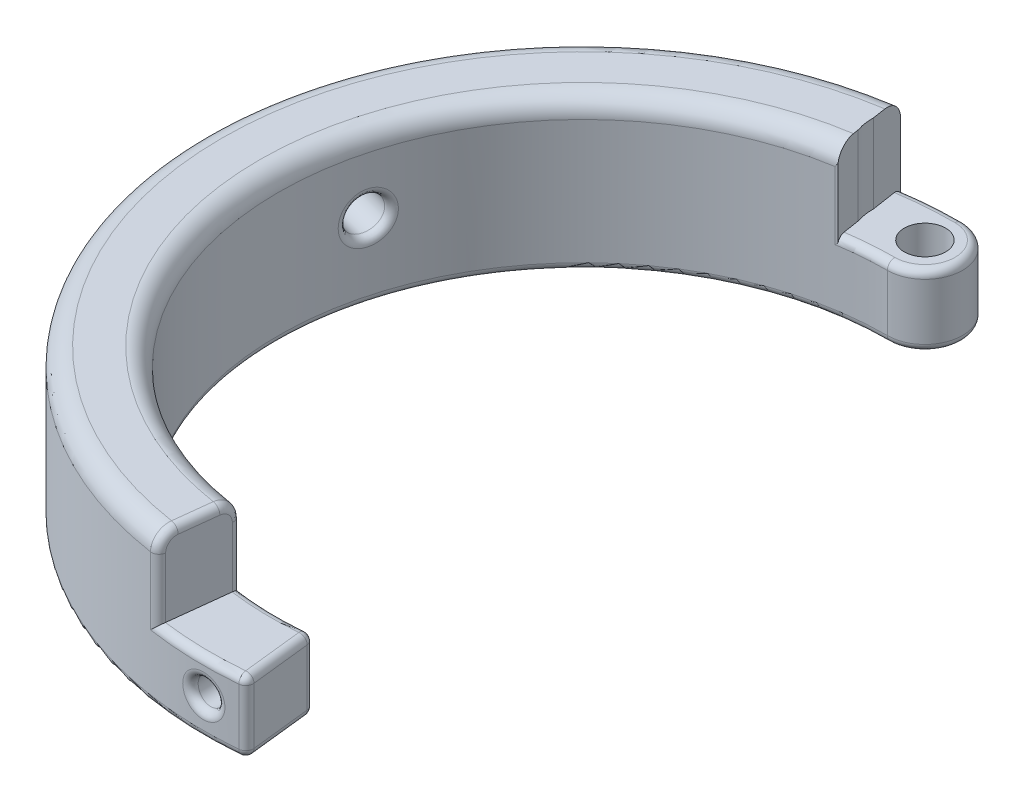
SolidWorks part; units mm, degrees
ref_plane "Front Plane" through (0, 0, 0) normal (0, 0, 1) x (1, 0, 0)
ref_plane "Top Plane" through (0, 0, 0) normal (0, 1, 0) x (1, 0, 0)
ref_plane "Right Plane" through (0, 0, 0) normal (1, 0, 0) x (0, 0, -1)
sketch "Sketch1" plane through (0, 0, 0) normal (0, 1, 0) x (1, 0, 0)
  line L0 (0, 50.5) -> (29.9823, 50.5) construction
  line L1 (0, 0) -> (0, 45.5) construction
  line L2 (0, 0) -> (-39.4042, -22.75) construction
  line L3 (4.5591, -41.2367) -> (5.4385, -49.1902)
  line L4 (0, 0) -> (4.4505, -40.2547) construction
  circle A0 centre (0, 45.5) radius 2.75
  arc A1 (0, 50.5) -> (0, 40.5) centre (0, 45.5) cw
  arc A2 (0, 50.5) -> (0, -50.5) centre (0, 0) ccw
  arc A3 (0, 40.5) -> (0, -40.5) centre (0, 0) ccw
  arc A4 (0, -40.5) -> (0, -50.5) centre (0, -45.5) cw construction
  circle A5 centre (-39.4042, -22.75) radius 2.75
  arc A6 (0, -40.5) -> (3.4793, -40.3503) centre (0, 0) ccw
  arc A7 (0, -50.5) -> (4.5343, -50.296) centre (0, 0) ccw
  arc A8 (4.5343, -50.296) -> (5.4385, -49.1902) centre (4.4445, -49.3001) ccw
  arc A9 (3.4793, -40.3503) -> (4.5591, -41.2367) centre (3.5652, -41.3466) cw
  dimension "D1" = 5.5
  dimension "D7" = 1
  dimension "D2" = 10
  dimension "D3" = 40.5
  dimension "D5" = 120
  dimension "D6" = 45.5
  dimension "D4" = 2
extrude "Boss-Extrude1" add sketch "Sketch1" along normal blind 20
sketch "Sketch3" plane through (0, 0, 0) normal (0, 0, 1) x (1, 0, 0)
  line L0 (4.5343, 20) -> (-50.5, 20) construction
  circle A0 centre (0, 15) radius 1.75
  circle A1 centre (0, 5) radius 1.75
  dimension "D1" = 3.5
  dimension "D4" = 3.5
  dimension "D2" = 5
  dimension "D3" = 5
extrude "Cut-Extrude2" cut sketch "Sketch3" along normal blind 71
sketch "Sketch2" plane through (0, 20, 0) normal (0, 1, 0) x (1, 0, 0)
  line L0 (0, -1000) -> (0, 49000) construction
  line L1 (5.4385, -49.1902) -> (4.5591, -41.2367)
  line L2 (5.4385, -49.1902) -> (4.5591, -41.2367) construction
  line L3 (-5.4385, -49.1902) -> (-4.5591, -41.2367) construction
  line L4 (-4.4505, -40.2547) -> (0, 0) construction
  line L5 (0, 0) -> (-5.5107, 35.9551) construction
  line L6 (0, 45.5) -> (-4.3301, 48) construction
  line L7 (0, 45.5) -> (-39.4042, -22.75) construction
  line L11 (-6.1357, 40.0325) -> (-6.1431, 40.0808) construction
  line L12 (-6.1431, 40.0808) -> (-6.629, 43.2514)
  line L13 (-5.5107, 35.9551) -> (-6.1357, 40.0325) construction
  line L16 (-6.629, 43.2514) -> (-6.9982, 45.66) construction
  line L17 (-6.9982, 45.66) -> (-7.6507, 49.9171)
  line L18 (-5.4193, -40.1358) -> (-6.5623, -50.0718)
  arc A0 (0, 50.5) -> (0, 40.5) centre (0, 45.5) ccw construction
  arc A1 (-6.9982, 45.66) -> (-6.629, 43.2514) centre (0, 45.5) ccw
  arc A2 (0, 52.5) -> (0, 38.5) centre (0, 45.5) ccw construction
  arc A3 (0, 40.5) -> (-4.6144, 40.2363) centre (0, 0) ccw construction
  arc A4 (0, 50.5) -> (-5.1544, 50.2363) centre (0, 0) ccw construction
  arc A5 (0, 50.5) -> (4.5343, -50.296) centre (0, 0) ccw
  arc A6 (4.5343, -50.296) -> (5.4385, -49.1902) centre (4.4445, -49.3001) ccw
  arc A7 (4.5591, -41.2367) -> (3.4793, -40.3503) centre (3.5652, -41.3466) ccw
  arc A8 (0, 40.5) -> (3.4793, -40.3503) centre (0, 0) ccw
  arc A9 (0, 40.5) -> (0, 50.5) centre (0, 45.5) ccw
  arc A10 (-7.6507, 49.9171) -> (-6.5623, -50.0718) centre (0, 0) ccw construction
  arc A11 (4.5343, -50.296) -> (5.4385, -49.1902) centre (4.4445, -49.3001) ccw construction
  arc A12 (4.5591, -41.2367) -> (3.4793, -40.3503) centre (3.5652, -41.3466) ccw construction
  arc A13 (-6.4367, 39.9852) -> (-5.4193, -40.1358) centre (0, 0) ccw construction
  arc A14 (-6.1431, 40.0808) -> (-6.4367, 39.9852) centre (-6.5956, 40.9725) cw
  arc A16 (-4.4505, -40.2547) -> (0, -40.5) centre (0, 0) ccw construction
  arc A17 (0, -40.5) -> (3.4793, -40.3503) centre (0, 0) ccw construction
  arc A18 (0, -50.5) -> (4.5343, -50.296) centre (0, 0) ccw construction
  arc A19 (-5.5495, -50.1942) -> (0, -50.5) centre (0, 0) ccw construction
  arc A20 (-5.4385, -49.1902) -> (-6.5623, -50.0718) centre (-6.4324, -49.0803) cw construction
  arc A21 (-4.5591, -41.2367) -> (-5.4193, -40.1358) centre (-5.5531, -41.1268) ccw construction
  arc A22 (-7.6507, 49.9171) -> (-6.5623, -50.0718) centre (0, 0) cw
  arc A23 (-5.4193, -40.1358) -> (-6.4367, 39.9852) centre (0, 0) ccw
  arc A24 (0, 50.5) -> (4.5343, -50.296) centre (0, 0) ccw construction
  arc A25 (-6.3062, 48.5385) -> (-6.9982, 45.66) centre (0, 45.5) ccw construction
  arc A28 (-5.7712, 41.5385) -> (-6.1431, 40.0808) centre (-6.5956, 40.9725) cw construction
  arc A29 (-6.629, 43.2514) -> (-5.7712, 41.5385) centre (0, 45.5) ccw construction
  dimension "D3" = 1
  dimension "D4" = 1
  dimension "D1" = 0
  dimension "D2" = 2
extrude "Cut-Extrude1" cut sketch "Sketch2" against normal blind 10.5
ref_plane "Plane1" through (-39.12, 0, -10.4822) normal (0.9659, 0, 0.2588) x (0, -1, 0)
sketch "Sketch4" plane through (0, 0, 0) normal (0, -1, 0) x (1, 0, 0)
  circle A0 centre (0, -45.5) radius 2.75 construction
  circle A1 centre (-39.4042, 22.75) radius 2.75 construction
  circle A2 centre (0, -45.5) radius 2.75
  circle A3 centre (-39.4042, 22.75) radius 2.75
  circle M8 centre (-39.4042, 22.75) radius 2.75
extrude "Boss-Extrude2" add sketch "Sketch4" along normal blind 3 from surface contours M8 region at (-39.4042, 0, 22.75) starting at face at (-17.7001, 20, -18.2497)
fillet "Fillet1" radius 2.5 2 edges at (-40.4967, 20, 0.5143) (-50.497, 20, 0.5496)
fillet "Fillet2" radius 1 19 edges at (-6.5623, 13.5, 50.0718) (-6.4551, 19.4521, 49.1397) (-5.9908, 20, 45.1039) (-5.4819, 19.0615, 40.68) (-3.8364, 9.5, -50.3541) (5, 9.5, -45.5) (-0.9759, 9.5, 40.4882) (4.1997, 9.5, 40.5736) (4.9988, 9.5, 45.2134) (5.2187, 9.5, 49.933) (5, 0, -45.5) (-40.4626, 0, 1.7412) (4.1997, 0, 40.5736) (4.9988, 0, 45.2134) (5.2187, 0, 49.933) (-5.4193, 13.5, 40.1358) (-3.2286, 9.5, -40.3711) (-1.0202, 9.5, 50.4897) (-50.449, 0, 2.2694)
sketch "Sketch6" plane through (-41.0271, 0, -3.3646) normal (0.9659, 0, 0.2588) x (0.2588, 0, -0.9659)
  circle A0 centre (7.3686, 10) radius 2.35
  point P2 (5.572, 8.3038)
  dimension "D1" = 4.7
  dimension "D2" = 10
extrude "Cut-Extrude3" cut sketch "Sketch6" against normal through all both and the other way through all
fillet "Fillet3" radius 1 4 edges at (-49.3213, 9.4623, -10.8472) (-39.6497, 10.5361, -8.2554) (1.7034, 5.4013, 50.4713) (1.7035, 4.5993, 40.4642)
